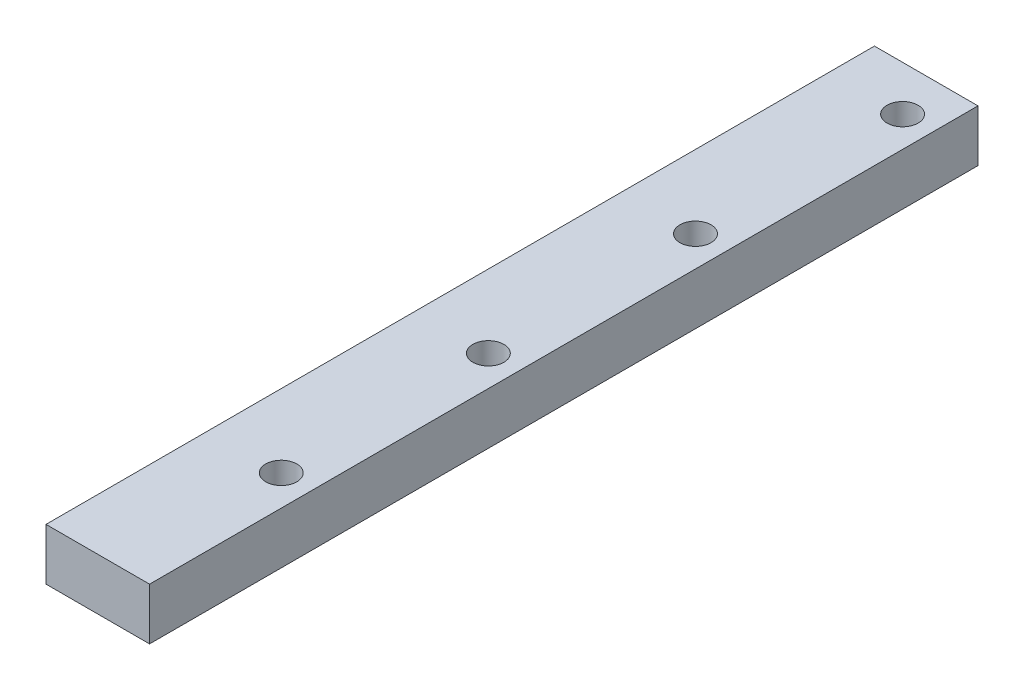
SolidWorks part; units mm, degrees
material "ABS"
ref_plane "Front Plane" through (0, 0, 0) normal (0, 0, 1) x (1, 0, 0)
ref_plane "Top Plane" through (0, 0, 0) normal (0, 1, 0) x (1, 0, 0)
ref_plane "Right Plane" through (0, 0, 0) normal (1, 0, 0) x (0, 0, -1)
sketch "Sketch1" plane through (0, 0, 0) normal (0, 0, 1) x (1, 0, 0)
  line L0 (20, 20.188) -> (0, 20.188)
  line L1 (0, 20.188) -> (0, 10.188)
  line L5 (20, 10.188) -> (20, 20.188)
  line L6 (0, 10.188) -> (20, 10.188)
  dimension "D1" = 20
  dimension "D2" = 10
  dimension "D3" = 10
extrude "Boss-Extrude1" add sketch "Sketch1" along normal blind 160
sketch "Sketch2" plane through (0, 20.188, 0) normal (0, 1, 0) x (1, 0, 0)
  circle A0 centre (14.1086, -8.6737) radius 3
extrude "Cut-Extrude1" cut sketch "Sketch2" against normal blind 140
pattern_linear "LPattern1" count 4 spacing 40 along (0, 0, 1) of "Cut-Extrude1"
